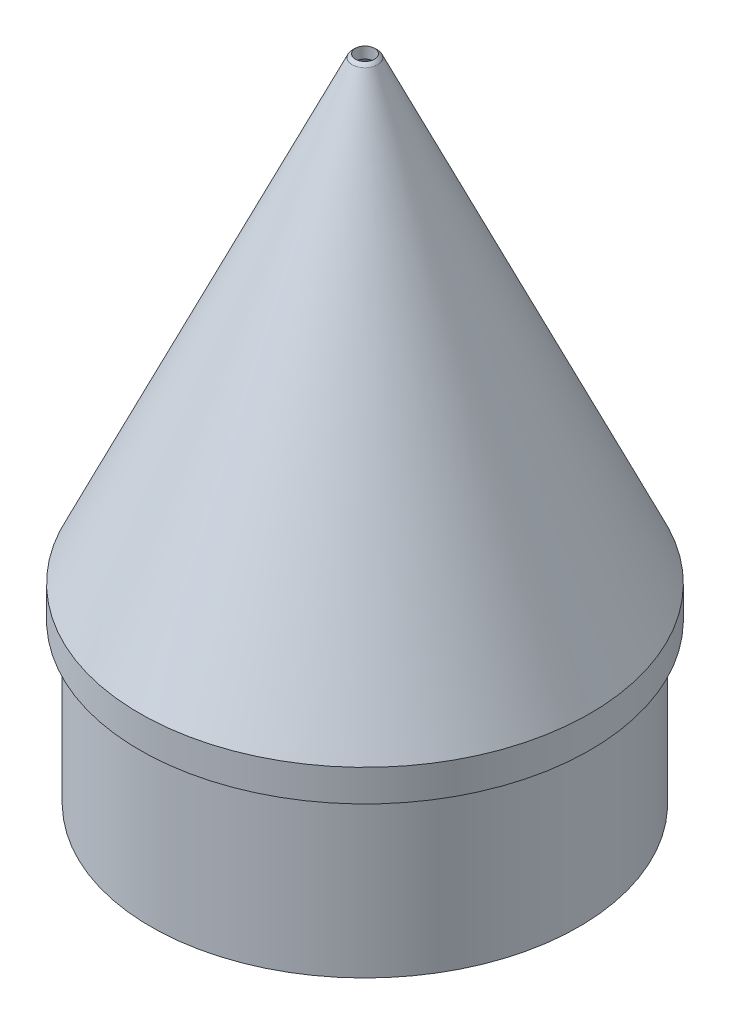
SolidWorks part; units mm, degrees
ref_plane "Front Plane" through (0, 0, 0) normal (0, 0, 1) x (1, 0, 0)
ref_plane "Top Plane" through (0, 0, 0) normal (0, 1, 0) x (1, 0, 0)
ref_plane "Right Plane" through (0, 0, 0) normal (1, 0, 0) x (0, 0, -1)
sketch "Sketch3" plane through (0, 0, 0) normal (0, 0, 1) x (1, 0, 0)
  line L1 (0, 0) -> (0, 155.682)
  line L4 (0, 0) -> (0, -50)
  line L5 (0, -50) -> (67.5, -50)
  line L6 (67.5, -50) -> (67.5, 0)
  line L9 (71, 0) -> (71, 10)
  line L11 (67.5, 0) -> (71, 0)
  line L12 (4, 153.682) -> (71, 10)
  line L13 (0, 229.1763) -> (0, 65.794) construction
  arc A0 (0, 155.682) -> (4, 153.682) centre (0, 150.682) cw
  point P11 (67.5, -50)
  point P14 (71, 10)
  dimension "Round yDim" = 2
  dimension "Lip Height" = 10
  dimension "Shoulder Height" = 50
  dimension "Half Angle" = 25
  dimension "Shoulder Diam" = 135
  dimension "Outer Diam" = 142
  dimension "Round xDim" = 8
revolve "Revolve1" add sketch "Sketch3" angle 360 about L1
shell "Shell1" thickness 2 removed face at (0, -50, -67.5)
sketch "Sketch7" plane through (0, 0, 0) normal (0, 1, 0) x (1, 0, 0)
  circle A0 centre (0, 0) radius 3
  dimension "D1" = 6
extrude "Cut-Extrude3" cut sketch "Sketch7" along normal through all
ref_plane "Plane1" through (0, 0, 0) normal (1, 0, 0) x (0, 0, -1)
sketch "Sketch8" plane through (0, 0, 0) normal (1, 0, 0) x (0, 0, -1)
  line L0 (-39.807, 40.9099) -> (-39.807, 20) construction
  line L1 (-44.807, 44.0901) -> (-44.807, 39.0901) construction
  line L2 (-44.807, 39.0901) -> (-39.807, 40.9099) construction
  line L3 (-39.807, 40.9099) -> (-39.807, 35.9099)
  line L4 (-44.807, 44.0901) -> (-44.807, 39.0901)
  line L5 (-44.807, 39.0901) -> (-39.807, 40.9099)
  line L6 (-39.807, 35.9099) -> (-44.807, 34.0901)
  line L7 (-44.807, 34.0901) -> (-57.5599, 34.0901)
  line L8 (-3, 151.0941) -> (-69, 9.5566) construction
  line L9 (-57.5599, 34.0901) -> (-44.807, 61.4387)
  line L10 (-44.807, 61.4387) -> (-44.807, 44.0901)
  dimension "D1" = 5
extrude "Boss-Extrude1" add sketch "Sketch8" along normal mid plane 15
sketch "Sketch9" plane through (0, 0, 0) normal (1, 0, 0) x (0, 0, -1)
  line L0 (-44.807, 39.0901) -> (-44.807, 60.1019) construction
  line L1 (-39.807, 40.9099) -> (-44.807, 39.0901) construction
  line L2 (-39.807, 35.9099) -> (-39.807, 40.9099) construction
  line L3 (-44.807, 34.0901) -> (-39.807, 35.9099) construction
  line L5 (-44.807, 39.0901) -> (-44.807, 60.1019)
  line L6 (-39.807, 40.9099) -> (-44.807, 39.0901)
  line L7 (-39.807, 35.9099) -> (-39.807, 40.9099)
  line L8 (-44.807, 34.0901) -> (-39.807, 35.9099)
  line L9 (-57.1133, 26.985) -> (-44.807, 34.0901)
  line L10 (-44.807, 34.0901) -> (-44.807, 39.0901) construction
  line L11 (-44.807, 60.1019) -> (-57.1133, 26.985)
  dimension "D1" = 120
extrude "Cut-Extrude4" cut sketch "Sketch9" against normal mid plane 3.5
pattern_circular "CirPattern1" count 2 over 360 about axis through (0, 0, 0) along (0, -1, 0) of "Boss-Extrude1", "Cut-Extrude4"
